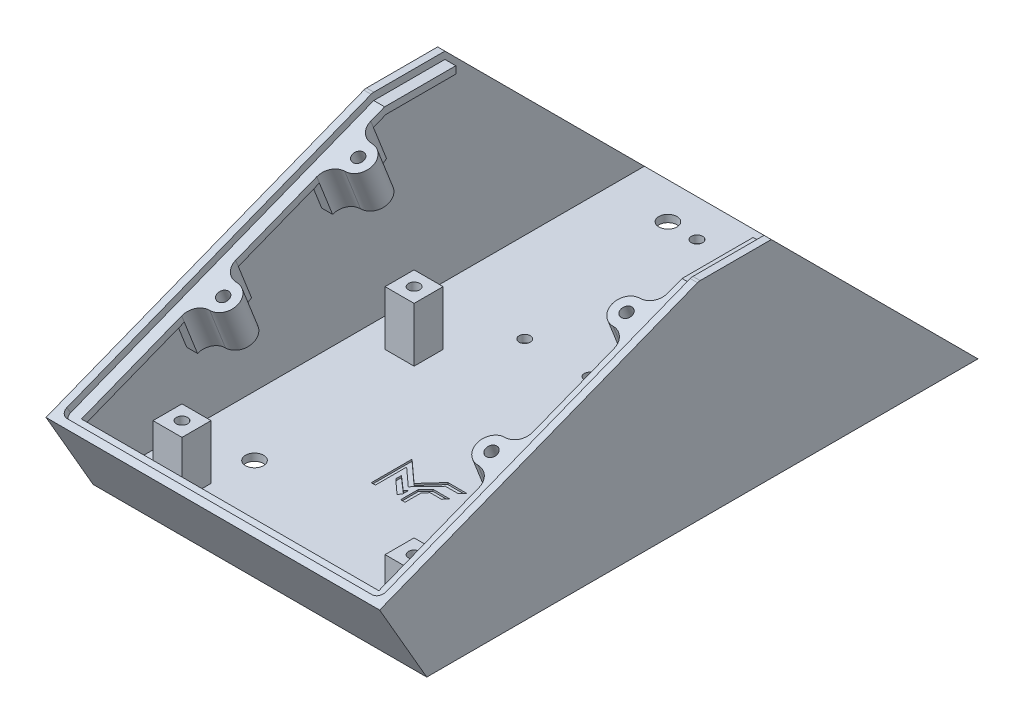
SolidWorks part; units mm, degrees
ref_plane "Plano frontal" through (0, 0, 0) normal (0, 0, 1) x (1, 0, 0)
ref_plane "Plano superior" through (0, 0, 0) normal (0, 1, 0) x (1, 0, 0)
ref_plane "Plano direito" through (0, 0, 0) normal (1, 0, 0) x (0, 0, -1)
sketch "Base" plane through (0, 0, 0) normal (0, 1, 0) x (1, 0, 0)
  line L0 (-44, 75) -> (44, -75) construction
  line L1 (-44, 75) -> (44, 75)
  line L2 (-44, 75) -> (-44, -75)
  line L3 (-44, -75) -> (44, -75)
  line L4 (44, 75) -> (44, -75)
  line L5 (44, 75) -> (-44, -75) construction
  dimension "D1" = 150
  dimension "D2" = 88
extrude "Ressalto-extrusão1" add sketch "Base" against normal blind 2 contours L4 L1 L2 L3 region at (0, 0, 0)
sketch "Base_Circuito" plane through (0, 0, 0) normal (0, 1, 0) x (1, 0, 0)
  line L0 (0, -32.5) -> (19.229, -32.5) construction
  line L1 (-44, 75) -> (44, 75) construction
  line L2 (-44, 75) -> (-44, -75) construction
  line L3 (-44, -75) -> (44, -75) construction
  line L4 (44, 75) -> (44, -75) construction
  line L5 (-44, 75) -> (44, -75) construction
  line L6 (-44, -75) -> (44, 75) construction
  line L7 (0, -75) -> (0, 75) construction
  line L8 (-35, 2.5) -> (35, 2.5) construction
  line L9 (-35, 2.5) -> (-35, -67.5) construction
  line L10 (-35, -67.5) -> (35, -67.5) construction
  line L11 (35, 2.5) -> (35, -67.5) construction
  line L12 (-35, 2.5) -> (35, -67.5) construction
  line L13 (-35, -67.5) -> (35, 2.5) construction
  line L14 (36, -68.5) -> (28, -68.5)
  line L15 (-35, -64.5) -> (-32, -64.5) construction
  line L16 (-35, -64.5) -> (-35, -67.5) construction
  line L17 (-35, -67.5) -> (-32, -67.5) construction
  line L18 (-32, -64.5) -> (-32, -67.5) construction
  line L19 (-35, -64.5) -> (-32, -67.5) construction
  line L20 (-35, -67.5) -> (-32, -64.5) construction
  line L21 (-36, -60.5) -> (-28, -60.5)
  line L22 (-36, -60.5) -> (-36, -68.5)
  line L23 (-36, -68.5) -> (-28, -68.5)
  line L24 (-28, -60.5) -> (-28, -68.5)
  line L25 (-36, -60.5) -> (-28, -68.5) construction
  line L26 (-36, -68.5) -> (-28, -60.5) construction
  line L27 (28, -60.5) -> (28, -68.5)
  line L28 (36, -60.5) -> (28, -60.5)
  line L29 (36, -60.5) -> (36, -68.5)
  line L30 (36, -4.5) -> (36, 3.5)
  line L31 (36, -4.5) -> (28, -4.5)
  line L32 (28, -4.5) -> (28, 3.5)
  line L33 (36, 3.5) -> (28, 3.5)
  line L34 (-36, 3.5) -> (-28, 3.5)
  line L35 (-28, -4.5) -> (-28, 3.5)
  line L36 (-36, -4.5) -> (-28, -4.5)
  line L37 (-36, -4.5) -> (-36, 3.5)
  circle A0 centre (-32, -64.5) radius 1.55 construction
  point P4 (0, 0)
  point P13 (0, -32.5)
  point P17 (0, 0)
  point P21 (-33.5, -66)
  dimension "D4" = 3.1
  dimension "D5" = 8
  dimension "D1" = 70
  dimension "D2" = 7.5
  dimension "D3" = 3
extrude "Ressalto-extrusão2" add sketch "Base_Circuito" along normal blind 15
sketch "Furo_Base_Circuito" plane through (0, 15, 0) normal (0, 1, 0) x (1, 0, 0)
  line L1 (-36, 3.5) -> (-28, 3.5) construction
  line L2 (-36, 3.5) -> (-36, -4.5) construction
  line L3 (-36, -4.5) -> (-28, -4.5) construction
  line L4 (-28, 3.5) -> (-28, -4.5) construction
  line L5 (-36, 3.5) -> (-28, -4.5) construction
  line L6 (-36, -4.5) -> (-28, 3.5) construction
  line L7 (28, 3.5) -> (36, 3.5) construction
  line L8 (28, 3.5) -> (28, -4.5) construction
  line L9 (28, -4.5) -> (36, -4.5) construction
  line L10 (36, 3.5) -> (36, -4.5) construction
  line L11 (28, 3.5) -> (36, -4.5) construction
  line L12 (28, -4.5) -> (36, 3.5) construction
  line L13 (-36, -60.5) -> (-28, -60.5) construction
  line L14 (-36, -60.5) -> (-36, -68.5) construction
  line L15 (-36, -68.5) -> (-28, -68.5) construction
  line L16 (-28, -60.5) -> (-28, -68.5) construction
  line L17 (-36, -60.5) -> (-28, -68.5) construction
  line L18 (-36, -68.5) -> (-28, -60.5) construction
  line L19 (28, -60.5) -> (36, -60.5) construction
  line L20 (28, -60.5) -> (28, -68.5) construction
  line L21 (28, -68.5) -> (36, -68.5) construction
  line L22 (36, -60.5) -> (36, -68.5) construction
  line L23 (28, -60.5) -> (36, -68.5) construction
  line L24 (28, -68.5) -> (36, -60.5) construction
  circle A0 centre (-32, -0.5) radius 1.55
  circle A1 centre (32, -0.5) radius 1.55
  circle A2 centre (-32, -64.5) radius 1.55
  circle A3 centre (32, -64.5) radius 1.55
  point P4 (-32, -0.5)
  point P11 (32, -0.5)
  point P18 (-32, -64.5)
  point P25 (32, -64.5)
  dimension "D1" = 3.1
extrude "Corte-extrusão1" cut sketch "Furo_Base_Circuito" against normal blind 15
sketch "Calha_nano_e_Conversor" plane through (0, 0, 0) normal (0, 1, 0) x (1, 0, 0)
  line L0 (36, 3.5) -> (28, 3.5) construction
  line L5 (21.5, 63.5) -> (42, 63.5) construction
  line L6 (21.5, 63.5) -> (21.5, 18.5) construction
  line L7 (21.5, 18.5) -> (42, 18.5) construction
  line L8 (42, 63.5) -> (42, 18.5) construction
  line L9 (-25.25, 58.5) -> (4.75, 58.5) construction
  line L10 (-25.25, 58.5) -> (-25.25, 23.5) construction
  line L11 (-25.25, 23.5) -> (4.75, 23.5) construction
  line L12 (4.75, 58.5) -> (4.75, 23.5) construction
  line L13 (-25.25, 58.5) -> (4.75, 23.5) construction
  line L14 (-25.25, 23.5) -> (4.75, 58.5) construction
  line L15 (21.5, 63.5) -> (42, 18.5) construction
  line L16 (21.5, 18.5) -> (42, 63.5) construction
  line L18 (42, 75) -> (42, -75) construction
  line L19 (-44, 75) -> (44, 75) construction
  line L20 (-44, -75) -> (44, -75) construction
  line L21 (44, 75) -> (44, -75) construction
  line L22 (31.75, 41) -> (31.75, 63.5) construction
  line L23 (31.75, 41) -> (42, 41) construction
  line L25 (-42, 75) -> (-42, -75) construction
  line L26 (-44, 75) -> (-44, -75) construction
  line L27 (21.5, 41) -> (-42, 41) construction
  line L29 (-1.25, 20.5) -> (-1.25, 14) construction
  line L30 (-4.75, 27) -> (2.25, 27) construction
  line L31 (-4.75, 27) -> (-4.75, 14) construction
  line L32 (-4.75, 14) -> (2.25, 14) construction
  line L33 (2.25, 27) -> (2.25, 14) construction
  line L34 (-4.75, 27) -> (2.25, 14) construction
  line L35 (-4.75, 14) -> (2.25, 27) construction
  line L36 (-10.25, 41) -> (-10.25, 50.2808) construction
  circle A0 centre (31.75, 52.25) radius 1.55
  circle A1 centre (31.75, 29.75) radius 1.55
  circle A3 centre (-1.25, 17.25) radius 1.55
  circle A4 centre (-19.25, 17.25) radius 1.55
  circle A5 centre (-1.25, 64.75) radius 1.55
  circle A6 centre (-19.25, 64.75) radius 1.55
  point P0 (31.75, 41)
  point P13 (-10.25, 41)
  point P23 (31.75, 41)
  point P39 (-1.25, 20.5)
  dimension "D8" = 3.1
  dimension "D5" = 30
  dimension "D6" = 35
  dimension "D1" = 20.5
  dimension "D2" = 45
  dimension "D3" = 15
  dimension "D7" = 2
  dimension "D4" = 2
  dimension "D9" = 7
  dimension "D10" = 13
  dimension "D11" = 7
  dimension "D12" = 2.5
extrude "Corte-extrusão2" cut sketch "Calha_nano_e_Conversor" against normal blind 15
sketch "Furo_Fixação" plane through (0, 0, 0) normal (0, 1, 0) x (1, 0, 0)
  line L0 (0, 0) -> (0, -17.0687) construction
  line L1 (44, -75) -> (27.5, -75) construction
  line L2 (44, -75) -> (44, -49) construction
  line L3 (44, -49) -> (27.5, -49) construction
  line L4 (27.5, -75) -> (27.5, -49) construction
  line L5 (44, -75) -> (27.5, -49) construction
  line L6 (44, -49) -> (27.5, -75) construction
  line L8 (44, 75) -> (27.5, 75) construction
  line L9 (44, 75) -> (44, 65) construction
  line L10 (44, 65) -> (27.5, 65) construction
  line L11 (27.5, 75) -> (27.5, 65) construction
  line L12 (44, 75) -> (27.5, 65) construction
  line L13 (44, 65) -> (27.5, 75) construction
  circle A0 centre (27.5, -49) radius 2.5
  circle A1 centre (-27.5, -49) radius 2.5
  circle A2 centre (27.5, 65) radius 2.5
  circle A3 centre (-27.5, 65) radius 2.5
  point P4 (35.75, -62)
  point P16 (35.75, 70)
  dimension "D3" = 5
  dimension "D1" = 16.5
  dimension "D2" = 26
  dimension "D4" = 16.5
  dimension "D5" = 10
extrude "Corte-extrusão3" cut sketch "Furo_Fixação" against normal blind 15
sketch "Tampa_Lateral" plane through (-44, 0, 0) normal (-1, 0, 0) x (0, 0, 1)
  line L0 (75, -2) -> (88, 20.5167)
  line L1 (-75, -2) -> (75, -2) construction
  line L2 (-75, -2) -> (75, -2)
  line L3 (0, -2) -> (0, 55) construction
  line L4 (88, 20.5167) -> (0, 55)
  line L5 (0, 55) -> (-20, 55)
  line L6 (-75, 0) -> (-20, 55)
  line L7 (-75, 0) -> (-77, -2)
  line L8 (-75, -2) -> (-77, -2)
  point P9 (0, 0)
  point P10 (0, 53.8341)
  point P13 (0, 0)
  point P14 (-14.5891, 60.4109)
  dimension "D1" = 120
  dimension "D2" = 26
  dimension "D3" = 20
  dimension "D4" = 45
extrude "Ressalto-extrusão3" add sketch "Tampa_Lateral" along normal blind 2
sketch "Esboço9" plane through (44, 0, 0) normal (1, 0, 0) x (0, 0, -1)
  line L0 (75, -2) -> (-75, -2) construction
  line L1 (75, -2) -> (-75, -2)
  line L2 (77, -2) -> (75, -2) construction
  line L3 (77, -2) -> (75, -2)
  line L4 (75, 0) -> (77, -2) construction
  line L5 (75, 0) -> (77, -2)
  line L6 (-75, -2) -> (-88, 20.5167) construction
  line L7 (-88, 20.5167) -> (0, 55) construction
  line L8 (0, 55) -> (20, 55) construction
  line L9 (20, 55) -> (75, 0) construction
  line L10 (-75, -2) -> (-88, 20.5167)
  line L11 (-88, 20.5167) -> (0, 55)
  line L12 (0, 55) -> (20, 55)
  line L13 (20, 55) -> (75, 0)
extrude "Ressalto-extrusão4" add sketch "Esboço9" along normal blind 2
ref_plane "Plano1" through (0, -32.976, 57.116) normal (0, -0.5, 0.866) x (1, 0, 0)
sketch "Esboço11" plane through (0, -32.976, 57.116) normal (0, -0.5, 0.866) x (1, 0, 0)
  line L0 (46, 61.7679) -> (46, 35.7679) construction
  line L1 (46, 61.7679) -> (46, 35.7679)
  line L2 (-46, 35.7679) -> (-46, 61.7679) construction
  line L3 (-46, 35.7679) -> (-46, 61.7679)
  line L4 (-46, 35.7679) -> (46, 35.7679)
  line L5 (-46, 61.7679) -> (46, 61.7679)
extrude "Ressalto-extrusão8" add sketch "Esboço11" against normal blind 2 contours L5 L1 L4 L3
sketch "Logo_MF" plane through (0, 0, 0) normal (0, 1, 0) x (1, 0, 0)
  line L0 (-6.0744, -38.2328) -> (-4.9408, -38.2328)
  line L1 (-4.9408, -38.2328) -> (-4.9408, -29.6129)
  line L2 (-4.9408, -29.6129) -> (-0.0018, -34.0994)
  line L3 (-0.0018, -34.0994) -> (4.9813, -28.8566)
  line L4 (4.9813, -28.8566) -> (8.5001, -28.8566)
  line L5 (8.5001, -28.8566) -> (9.6281, -27.6148)
  line L6 (9.6281, -27.6148) -> (4.4376, -27.6148)
  line L7 (4.4376, -27.6148) -> (0, -32.5)
  line L8 (0, -32.5) -> (-6.0744, -26.9821)
  line L9 (-6.0744, -26.9821) -> (-6.0744, -38.2328)
  line L10 (-3.6321, -32.3521) -> (-3.6321, -33.9226)
  line L11 (-3.6321, -33.9226) -> (0.2483, -37.4476)
  line L12 (0.2483, -37.4476) -> (0.9292, -36.698)
  line L13 (0.9292, -36.698) -> (0.9292, -34.9779)
  line L14 (0.9292, -34.9779) -> (0.2472, -35.7287)
  line L15 (0.2472, -35.7287) -> (-3.6321, -32.3521)
  line L16 (2.0292, -38.2328) -> (2.0292, -33.3908)
  line L17 (2.0292, -33.3908) -> (4.0292, -31.2866)
  line L18 (4.0292, -31.2866) -> (8.7127, -31.2866)
  line L19 (8.7127, -31.2866) -> (7.5603, -32.499)
  line L20 (7.5603, -32.499) -> (4.4381, -32.499)
  line L21 (4.4381, -32.499) -> (3.2442, -33.7551)
  line L22 (3.2442, -33.7551) -> (3.2442, -38.2328)
  line L23 (3.2442, -38.2328) -> (2.0292, -38.2328)
  line L24 (-44, 75) -> (-44, -73.8453) construction
  line L25 (-44, 75) -> (44, 75) construction
  line L26 (0, 0) -> (0, -32.5) construction
  line L27 (-32, -0.5) -> (-32, -64.5) construction
  line L28 (-32, -32.5) -> (-23.5182, -32.5) construction
  point P38 (0, 0)
  dimension "D1" = 2.43
  dimension "D2" = 6.97
  dimension "D3" = 1.1
  dimension "D4" = 37.9256
  dimension "D5" = 39.0592
  dimension "D6" = 40.3679
  dimension "D7" = 43.9982
  dimension "D8" = 44.2472
  dimension "D9" = 44.2483
  dimension "D10" = 47.2442
  dimension "D11" = 53.6281
  dimension "D12" = 48.0292
  dimension "D13" = 48.4376
  dimension "D14" = 48.4381
  dimension "D15" = 48.9813
  dimension "D16" = 51.5603
  dimension "D17" = 52.5001
  dimension "D18" = 52.7127
  dimension "D19" = 101.9821
  dimension "D20" = 104.6129
  dimension "D21" = 107.3521
  dimension "D22" = 108.9226
  dimension "D23" = 109.9779
  dimension "D24" = 113.2328
extrude "Corte-extrusão5" cut sketch "Logo_MF" against normal blind 0.5
sketch "Esboço14" plane through (46, 0, 0) normal (1, 0, 0) x (0, 0, -1)
  line L0 (0, 55) -> (-86.1167, 21.2547) construction
  line L1 (0, 55) -> (-86.1167, 21.2547) construction
  line L2 (-86.1167, 21.2547) -> (-88, 20.5167)
  line L3 (-88, 20.5167) -> (-86.2679, 21.5167)
  line L4 (-86.2679, 21.5167) -> (-86.1167, 21.2547)
extrude "Corte-extrusão6" cut sketch "Esboço14" against normal up to surface (92 mm away) up to face at (-46, 24.184, 34.0549)
sketch "Esboço15" plane through (-44, 0, 0) normal (1, 0, 0) x (0, 0, -1)
  line L3 (-85.387, 19.3925) -> (0.7297, 53.1379)
  line L4 (-85.1053, 19.5029) -> (0.3779, 53)
  line L5 (0.7557, 51) -> (20, 51)
  line L6 (0, 53) -> (20, 53)
  line L7 (0.3779, 53) -> (20, 53)
  line L8 (-84.0939, 17.7511) -> (0.7557, 51)
  line L9 (0.3779, 51) -> (20, 51) construction
  line L10 (-84.6573, 17.5304) -> (1.1076, 51.1379) construction
  line L11 (20, 53) -> (20, 51)
  line L13 (-86.1167, 21.2547) -> (-73.8453, 0) construction
  line L14 (-85.387, 19.3925) -> (0.3779, 53) construction
  line L15 (-86.1167, 21.2547) -> (-73.8453, 0)
  point P14 (0, 0)
  point P15 (0, 0)
  point P16 (0, 0)
  point P17 (0, 0)
  line M8 (-86.1167, 21.2547) -> (-73.8453, 0)
  dimension "D1" = 2
  dimension "D2" = 2
  dimension "D3" = 2
  dimension "D4" = 2
extrude "Ressalto-extrusão9" add sketch "Esboço15" along normal blind 3 contours L11 L7 L4 L8 L5 M8 region at (-44, 38.2389, 32.8526)
sketch "Esboço16" plane through (44, 0, 0) normal (-1, 0, 0) x (0, 0, 1)
  line L12 (85.1053, 19.5029) -> (84.0939, 17.7511) construction
  line L13 (85.1053, 19.5029) -> (84.0939, 17.7511)
  line L14 (84.0939, 17.7511) -> (-0.7557, 51) construction
  line L15 (84.0939, 17.7511) -> (-0.7557, 51)
  line L16 (85.1053, 19.5029) -> (-0.3779, 53) construction
  line L17 (85.1053, 19.5029) -> (-0.3779, 53)
  line L18 (-0.3779, 53) -> (-20, 53) construction
  line L19 (-0.3779, 53) -> (-20, 53)
  line L20 (-0.7557, 51) -> (-20, 51) construction
  line L21 (-0.7557, 51) -> (-20, 51)
  line L22 (-20, 53) -> (-20, 51) construction
  line L23 (-20, 53) -> (-20, 51)
extrude "Ressalto-extrusão10" add sketch "Esboço16" along normal blind 3 contours L23 L21 L15 L13 L17 L19
sketch "Esboço17" plane through (0, 45.8167, 17.9536) normal (0, 0.9311, 0.3648) x (1, 0, 0)
  line L1 (-41, -28.4259) -> (-33, -28.4259) construction
  line L3 (-41, -36.4259) -> (-33, -36.4259) construction
  line L4 (-33, -28.4259) -> (-33, -36.4259) construction
  line L5 (-41, -28.4259) -> (-33, -36.4259) construction
  line L6 (-41, -36.4259) -> (-33, -28.4259) construction
  line L7 (-41, -24.4259) -> (-44, -24.4259)
  line L10 (-41, -28.4259) -> (-33, -28.4259) construction
  line L12 (-44, -72.4259) -> (-44, 20.0665) construction
  line L13 (-41, -40.4259) -> (-44, -40.4259)
  line L14 (-44, 19.6886) -> (-44, -72.1233) construction
  line L15 (0, 0) -> (0, -16.5987) construction
  line L16 (-44, 19.6886) -> (-44, -72.1233) construction
  line L17 (-44, -24.4259) -> (-44, -40.4259)
  line L20 (41, -40.4259) -> (44, -40.4259)
  line L23 (-44, -72.4259) -> (44, -72.4259) construction
  line L24 (44, -24.4259) -> (44, -40.4259)
  line L25 (41, -24.4259) -> (44, -24.4259)
  line L26 (-41, 15.5741) -> (-44, 15.5741)
  line L27 (-44, 15.5741) -> (-44, -0.4259)
  line L28 (-41, -0.4259) -> (-44, -0.4259)
  line L29 (41, -0.4259) -> (44, -0.4259)
  line L30 (44, 15.5741) -> (44, -0.4259)
  line L31 (41, 15.5741) -> (44, 15.5741)
  arc A1 (-41, -24.4259) -> (-37, -28.4259) centre (-37, -24.4259) ccw
  arc A2 (-37, -36.4259) -> (-41, -40.4259) centre (-37, -40.4259) ccw
  circle A3 centre (-37, -32.4259) radius 1.55
  arc A4 (-37, -36.4259) -> (-37, -28.4259) centre (-37, -32.4259) ccw
  circle A5 centre (37, -32.4259) radius 1.55
  arc A6 (37, -36.4259) -> (41, -40.4259) centre (37, -40.4259) cw
  arc A7 (41, -24.4259) -> (37, -28.4259) centre (37, -24.4259) cw
  arc A8 (37, -36.4259) -> (37, -28.4259) centre (37, -32.4259) cw
  arc A9 (-37, 3.5741) -> (-37, 11.5741) centre (-37, 7.5741) ccw
  arc A10 (-41, 15.5741) -> (-37, 11.5741) centre (-37, 15.5741) ccw
  arc A11 (-37, 3.5741) -> (-41, -0.4259) centre (-37, -0.4259) ccw
  circle A12 centre (-37, 7.5741) radius 1.55
  arc A13 (41, 15.5741) -> (37, 11.5741) centre (37, 15.5741) cw
  arc A14 (37, 3.5741) -> (37, 11.5741) centre (37, 7.5741) cw
  arc A15 (37, 3.5741) -> (41, -0.4259) centre (37, -0.4259) cw
  circle A16 centre (37, 7.5741) radius 1.55
  point P0 (-37, -32.4259)
  point P14 (-42.5, -40.4259)
  dimension "D3" = 3.1
  dimension "D1" = 4
  dimension "D2" = 32
  dimension "D4" = 2
extrude "Ressalto-extrusão11" add sketch "Esboço17" against normal blind 12
sketch "Esboço19" plane through (41, 0, 0) normal (-1, 0, 0) x (0, 0, 1)
  line L0 (85.1053, 19.5029) -> (84.0939, 17.7511) construction
  line L1 (85.1053, 19.5029) -> (84.0939, 17.7511) construction
  line L2 (85.1053, 19.5029) -> (55.5928, 31.0675) construction
  line L3 (85.1053, 19.5029) -> (55.5928, 31.0675) construction
  line L4 (84.0939, 17.7511) -> (54.8631, 29.2054) construction
  line L5 (84.0939, 17.7511) -> (54.8631, 29.2054) construction
  line L6 (83.222, 20.2409) -> (82.3619, 18.7511) construction
  line L7 (82.3619, 18.7511) -> (82.2106, 18.4891) construction
  line L8 (83.3733, 20.5029) -> (82.3619, 18.7511) construction
  line L9 (85.1053, 19.5029) -> (83.222, 20.2409)
  line L10 (83.222, 20.2409) -> (82.2106, 18.4891)
  line L11 (82.2106, 18.4891) -> (84.0939, 17.7511)
  line L12 (84.0939, 17.7511) -> (85.1053, 19.5029)
  dimension "D1" = 2
extrude "Ressalto-extrusão12" add sketch "Esboço19" along normal up to surface (82 mm away) up to face at (-41, 24.3817, 69.9138)
fillet "Filete1" radius 2 2 edges at (44, 20.3788, 85.611) (-44, 20.3788, 85.611)
fillet "Filete2" radius 2 2 edges at (45, 55, 0) (-45, 55, 0)
equation "\"D4@Calha_nano_e_Conversor\"=\"D7@Calha_nano_e_Conversor\""
